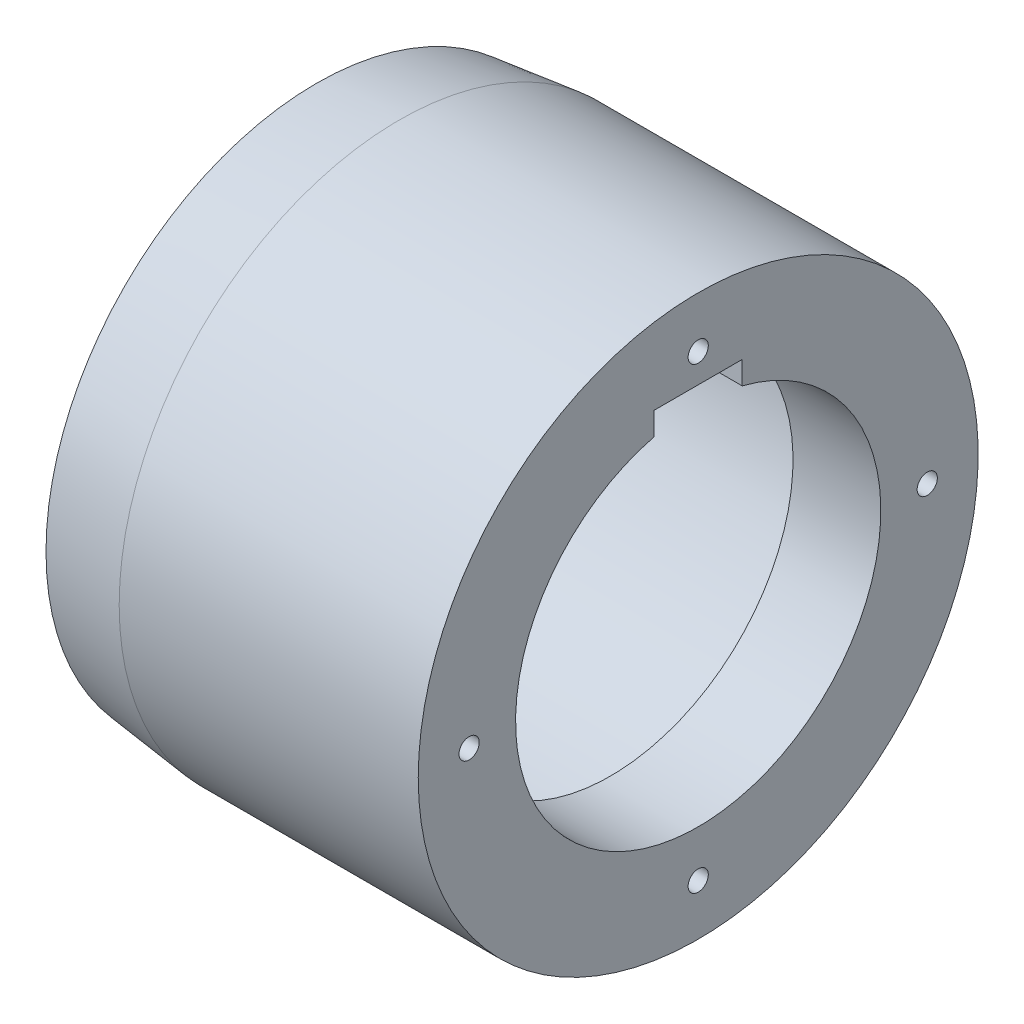
SolidWorks part; units mm, degrees
material "6061 Alloy"
ref_plane "Front Plane" through (0, 0, 0) normal (0, 0, 1) x (1, 0, 0)
ref_plane "Top Plane" through (0, 0, 0) normal (0, 1, 0) x (1, 0, 0)
ref_plane "Right Plane" through (0, 0, 0) normal (1, 0, 0) x (0, 0, -1)
sketch "Sketch1" plane through (0, 0, 0) normal (0, 0, 1) x (1, 0, 0)
  line L0 (0, 0) -> (74.8253, 0) construction
  line L1 (13, 44) -> (60, 44)
  line L2 (60, 44) -> (60, 28.702)
  line L5 (40, 42.5) -> (0, 42.5)
  line L6 (0, 42.5) -> (13, 44)
  line L7 (0, 0) -> (0, 42.5) construction
  line L9 (46.1983, 36) -> (46.1983, 28.702)
  line L10 (46.1983, 28.702) -> (60, 28.702)
  line L13 (40, 42.5) -> (40, 41.0807)
  line L14 (40, 41.0807) -> (46.1983, 41.0807)
  line L15 (46.1983, 41.0807) -> (46.1983, 36)
  dimension "D1" = 1.4193
  dimension "D2" = 42.5
  dimension "D3" = 13
  dimension "D4" = 6.1983
  dimension "D5" = 28.702
  dimension "D6" = 1.5
  dimension "D7" = 13.8017
  dimension "D8" = 46.1983
revolve "Revolve1" add sketch "Sketch1" angle 360 about L0
sketch "Sketch2" plane through (60, 0, 0) normal (1, 0, 0) x (0, 0, -1)
  line L0 (-36, 0) -> (0, 0) construction
  circle A3 centre (-36, 0) radius 1.5875
  circle A4 centre (0, 36) radius 1.5875
  circle A5 centre (36, 0) radius 1.5875
  circle A6 centre (0, -36) radius 1.5875
  point P2 (0, -35)
  point P10 (0, 0)
  point P16 (0, 0)
  dimension "D2" = 3.175
  dimension "D1" = 36
  dimension "D3" = 4
extrude "Cut-Extrude1" cut sketch "Sketch2" against normal blind 20
sketch "Sketch3" plane through (46.1983, 0, 0) normal (-1, 0, 0) x (0, 0, 1)
  line L1 (-6.9203, 25.9452) -> (6.9203, 25.9452)
  line L2 (-6.9203, 25.9452) -> (-6.9203, 31.4588)
  line L3 (-6.9203, 31.4588) -> (6.9203, 31.4588)
  line L4 (6.9203, 25.9452) -> (6.9203, 31.4588)
  line L5 (-6.9203, 25.9452) -> (6.9203, 31.4588) construction
  line L6 (-6.9203, 31.4588) -> (6.9203, 25.9452) construction
  circle A0 centre (0, 0) radius 28.702 construction
  point P0 (0, 28.702)
extrude "Cut-Extrude2" cut sketch "Sketch3" against normal blind 20
